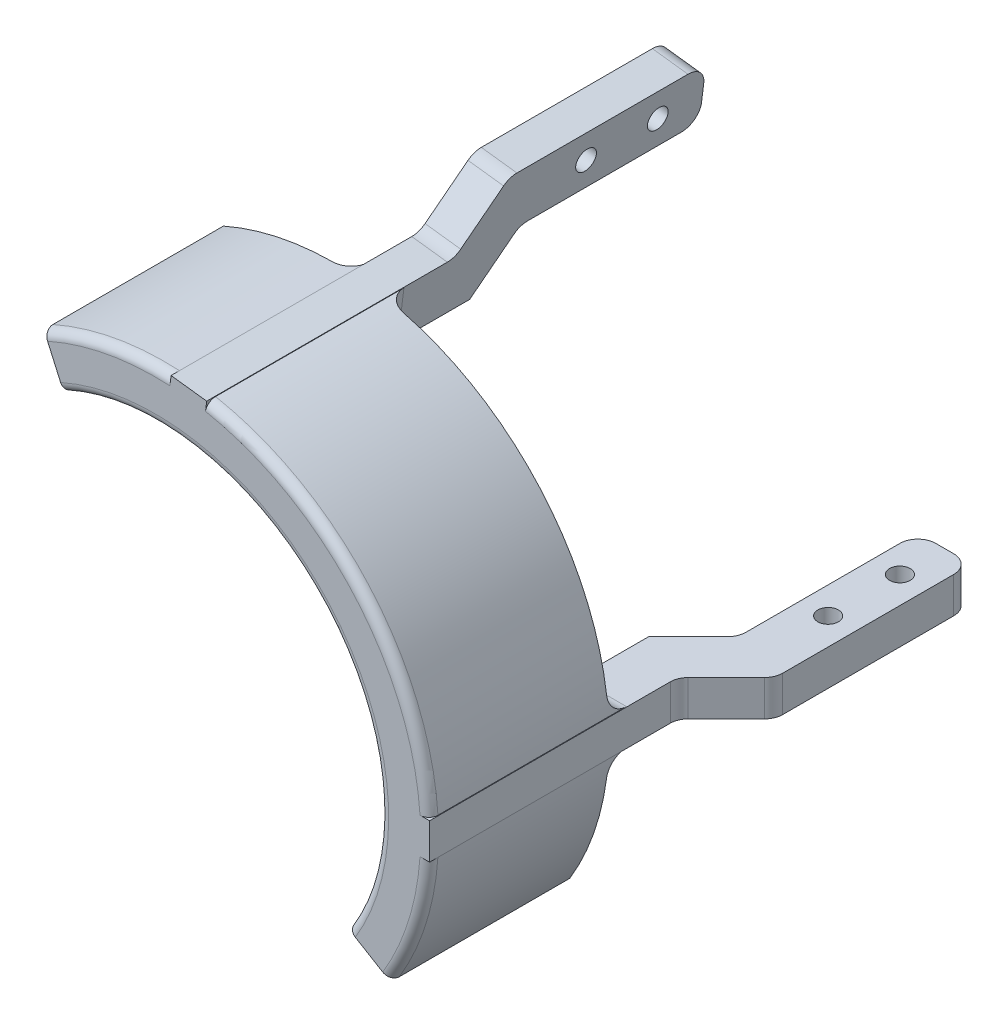
SolidWorks part; units mm, degrees
material "聚脂树脂"
ref_plane "前视基准面" through (0, 0, 0) normal (0, 0, 1) x (1, 0, 0)
ref_plane "上视基准面" through (0, 0, 0) normal (0, 1, 0) x (1, 0, 0)
ref_plane "右视基准面" through (0, 0, 0) normal (1, 0, 0) x (0, 0, -1)
other "Configuration Table"
sketch "草图1" plane through (0, 0, 0) normal (0, 1, 0) x (1, 0, 0)
  line L0 (0, 0) -> (0, 40.389) construction
  line L1 (0, 0) -> (49.8304, 0) construction
  line L2 (0, 35) -> (25, 35) construction
  line L3 (25, 35) -> (25, 30) construction
  line L4 (15, 20) -> (25, 30)
  line L5 (25, 30) -> (15, 20) construction
  line L6 (25, -30) -> (15, -20) construction
  line L7 (25, 30) -> (25, 40)
  line L8 (25, -35) -> (25, -30) construction
  line L9 (0, -35) -> (25, -35) construction
  line L10 (0, 35) -> (0, -35) construction
  line L12 (30.5635, 25.664) -> (30.5635, 37.664)
  line L13 (30.5635, 25.664) -> (19.9569, 15.0574)
  line L14 (25, 40) -> (30, 45)
  line L17 (30.5635, 37.664) -> (36, 43.1005)
  line L18 (30, 45) -> (30, 65)
  line L19 (30, 65) -> (36, 65)
  line L20 (36, 65) -> (36, 43.1005)
  line L21 (33, 65) -> (33, 39.979) construction
  line L22 (25, 30) -> (25, 10)
  line L23 (25, 10) -> (30.5635, 10)
  line L24 (30.5635, 10) -> (30.5635, 25.664)
  arc A0 (15, -20) -> (15, 20) centre (0, 0) ccw construction
  arc A1 (15, 20) -> (19.9569, 15.0574) centre (0, 0) cw
  circle A4 centre (33, 60) radius 1.15
  circle A5 centre (33, 52) radius 1.15
  dimension "D3" = 50
  dimension "D11" = 0
  dimension "D12" = 20
  dimension "D13" = 2.3
  dimension "D14" = 2.3
  dimension "D15" = 8
  dimension "D16" = 5
  dimension "D17" = 20
  dimension "D1" = 5
  dimension "D2" = 25
  dimension "D4" = 35
  dimension "D5" = 45
  dimension "D6" = 7
  dimension "D7" = 135
  dimension "D8" = 10
  dimension "D9" = 5
  dimension "D10" = 6
  dimension "D18" = 15
  dimension "D19" = 12
extrude "凸台-拉伸1" add sketch "草图1" along normal blind 4 contours L7 L22 L13 L12 L17 L20 L19 L18 L14 A5 A4 | L23 L24 L13 L22 region at (30.6405, 0, -43.7741) region at (27.982, 0, -16.5412)
fillet "圆角1" radius 2 5 edges at (30.5635, 2, -37.664) (30, 2, -45) (36, 2, -43.1005) (36, 2, -65) (30, 2, -65)
ref_plane "基准面1" through (0, 2, 0) normal (0, 1, 0) x (1, 0, 0)
ref_axis "基准轴1" through (0, 2, -67.7528) along (0, 0, 1)
sketch "草图2" plane through (0, 2, 0) normal (0, 1, 0) x (1, 0, 0)
  line L0 (25, 30) -> (30.5635, 30)
  line L8 (25, 10) -> (30.5635, 10)
  line L10 (30.5635, 10) -> (30.5635, 36.8355)
  line L27 (31.1492, 38.2497) -> (35.4142, 42.5147)
  line L28 (36, 43.9289) -> (36, 63)
  line L29 (34, 65) -> (32, 65)
  line L30 (30, 63) -> (30, 45.8284)
  line L31 (29.4142, 44.4142) -> (25, 40)
  line L32 (25, 40) -> (25, 10)
  line L33 (25, 10) -> (30.5635, 10)
  line L34 (30.5635, 10) -> (30.5635, 36.8355)
  line L35 (31.1492, 38.2497) -> (35.4142, 42.5147)
  line L36 (36, 43.9289) -> (36, 63)
  line L37 (34, 65) -> (32, 65)
  line L38 (30, 63) -> (30, 45.8284)
  line L39 (29.4142, 44.4142) -> (25, 40)
  line L40 (25, 40) -> (25, 10)
  arc A8 (31.1492, 38.2497) -> (30.5635, 36.8355) centre (32.5635, 36.8355) ccw
  arc A17 (35.4142, 42.5147) -> (36, 43.9289) centre (34, 43.9289) ccw
  arc A26 (36, 63) -> (34, 65) centre (34, 63) ccw
  arc A27 (32, 65) -> (30, 63) centre (32, 63) ccw
  arc A28 (29.4142, 44.4142) -> (30, 45.8284) centre (28, 45.8284) ccw
  arc A31 (31.1492, 38.2497) -> (30.5635, 36.8355) centre (32.5635, 36.8355) ccw
  arc A32 (35.4142, 42.5147) -> (36, 43.9289) centre (34, 43.9289) ccw
  arc A33 (36, 63) -> (34, 65) centre (34, 63) ccw
  arc A34 (32, 65) -> (30, 63) centre (32, 63) ccw
  arc A35 (29.4142, 44.4142) -> (30, 45.8284) centre (28, 45.8284) ccw
  dimension "D2" = 20
  dimension "D1" = 0
revolve "旋转2" add sketch "草图2" angle 114 about axis through (0, 2, -67.7528) along (0, 0, 1) region at (27.7817, 2, -20) other way angle 31
pattern_circular "阵列(圆周)4" count 2 every 83 about axis through (0, 2, -67.7528) along (0, 0, 1) of "凸台-拉伸1", "圆角1"
fillet "圆角2" radius 1 4 edges at (29.1687, -7.1275, -10) (22.8907, 22.252, -10) (-5.5047, 32.0637, -10) (18.7239, 18.5655, -10)
fillet "圆角3" radius 2 4 edges at (5.3668, 29.2984, -30) (1.3967, 29.7859, -30) (27.749, 4, -30) (27.749, 0, -30)
